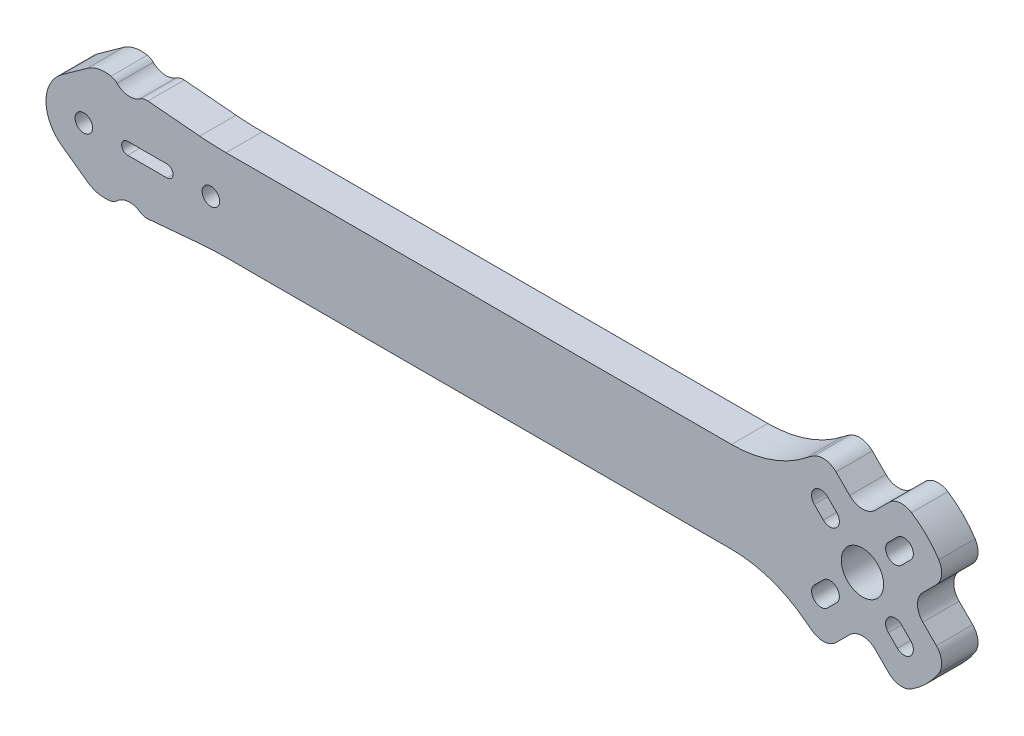
SolidWorks part; units mm, degrees
material "Thornel Mat VMA"
ref_plane "Front Plane" through (0, 0, 0) normal (0, 0, 1) x (1, 0, 0)
ref_plane "Top Plane" through (0, 0, 0) normal (0, 1, 0) x (1, 0, 0)
ref_plane "Right Plane" through (0, 0, 0) normal (1, 0, 0) x (0, 0, -1)
sketch "Sketch1" plane through (0, 0, 0) normal (0, 0, 1) x (1, 0, 0)
  line L0 (6.8589, 6.8589) -> (5.374, 5.374) construction
  line L2 (7.955, 5.7629) -> (6.47, 4.278)
  line L3 (5.7629, 7.955) -> (4.278, 6.47)
  line L4 (-6.8589, 6.8589) -> (-5.374, 5.374) construction
  line L5 (-5.7629, 7.955) -> (-4.278, 6.47)
  line L6 (-7.955, 5.7629) -> (-6.47, 4.278)
  line L7 (5.374, -5.374) -> (-5.374, 5.374) construction
  line L8 (6.8589, -6.8589) -> (5.374, -5.374) construction
  line L9 (5.7629, -7.955) -> (4.278, -6.47)
  line L11 (7.955, -5.7629) -> (6.47, -4.278)
  line L12 (-6.8589, -6.8589) -> (-5.374, -5.374) construction
  line L13 (-7.955, -5.7629) -> (-6.47, -4.278)
  line L14 (-5.7629, -7.955) -> (-4.278, -6.47)
  line L15 (-118.078, -8.4386) -> (-109.5245, -7.6903)
  line L16 (-105.1667, -7.5) -> (-21.6506, -7.5)
  line L17 (-4.367, -12.2159) -> (-2.1213, -9.9702)
  line L18 (2.1213, -9.9702) -> (4.367, -12.2159)
  line L19 (12.2159, -4.367) -> (9.9702, -2.1213)
  line L20 (9.9702, 2.1213) -> (12.2159, 4.367)
  line L21 (4.367, 12.2159) -> (2.1213, 9.9702)
  line L22 (-2.1213, 9.9702) -> (-4.367, 12.2159)
  line L23 (-21.6506, 7.5) -> (-105.1667, 7.5)
  line L24 (-109.5245, 7.6903) -> (-118.078, 8.4386)
  line L25 (-128.1078, 8.1033) -> (-132.3227, 5.0768)
  line L26 (-132.3227, -5.0768) -> (-128.1078, -8.1033)
  line L27 (-121.4272, 1) -> (-114.9272, 1)
  line L28 (-114.9272, -1) -> (-121.4272, -1)
  line L29 (0, 0) -> (-2.4749, 0) construction
  line L30 (-2.4749, 0) -> (-2.4749, 2.4749) construction
  circle A1 centre (0, 0) radius 3.5
  arc A20 (-124.1818, -8.9388) -> (-123.1893, -8.4119) centre (-124.5857, -6.98) ccw
  arc A21 (-119.3893, -8.0916) -> (-123.1893, -8.4119) centre (-121.0948, -10.5597) ccw
  arc A22 (-119.3893, -8.0916) -> (-118.078, -8.4386) centre (-118.2523, -6.4462) ccw
  arc A23 (-105.1667, -7.5) -> (-109.5245, -7.6903) centre (-105.1667, -57.5) ccw
  arc A24 (-9.2788, -11.7857) -> (-21.6506, -7.5) centre (-21.6506, -27.5) ccw
  arc A25 (-9.2788, -11.7857) -> (-8.1105, -12.6183) centre (0, 0) ccw
  arc A26 (-8.1105, -12.6183) -> (-4.367, -12.2159) centre (-6.4884, -10.0946) ccw
  arc A27 (2.1213, -9.9702) -> (-2.1213, -9.9702) centre (0, -12.0915) ccw
  arc A28 (4.367, -12.2159) -> (8.1105, -12.6183) centre (6.4884, -10.0946) ccw
  arc A29 (8.1105, -12.6183) -> (12.6183, -8.1105) centre (0, 0) ccw
  arc A30 (12.6183, -8.1105) -> (12.2159, -4.367) centre (10.0946, -6.4884) ccw
  arc A31 (9.9702, 2.1213) -> (9.9702, -2.1213) centre (12.0915, 0) ccw
  arc A32 (12.2159, 4.367) -> (12.6183, 8.1105) centre (10.0946, 6.4884) ccw
  arc A33 (12.6183, 8.1105) -> (8.1105, 12.6183) centre (0, 0) ccw
  arc A34 (8.1105, 12.6183) -> (4.367, 12.2159) centre (6.4884, 10.0946) ccw
  arc A35 (-2.1213, 9.9702) -> (2.1213, 9.9702) centre (0, 12.0915) ccw
  arc A36 (-4.367, 12.2159) -> (-8.1105, 12.6183) centre (-6.4884, 10.0946) ccw
  arc A37 (-8.1105, 12.6183) -> (-9.2788, 11.7857) centre (0, 0) ccw
  arc A38 (-21.6506, 7.5) -> (-9.2788, 11.7857) centre (-21.6506, 27.5) ccw
  arc A39 (-109.5245, 7.6903) -> (-105.1667, 7.5) centre (-105.1667, 57.5) ccw
  arc A40 (-118.078, 8.4386) -> (-119.3893, 8.0916) centre (-118.2523, 6.4462) ccw
  arc A41 (-123.1893, 8.4119) -> (-119.3893, 8.0916) centre (-121.0948, 10.5597) ccw
  arc A42 (-123.1893, 8.4119) -> (-124.1818, 8.9388) centre (-124.5857, 6.98) ccw
  arc A43 (-124.1818, 8.9388) -> (-128.1078, 8.1033) centre (-125.1915, 4.0418) ccw
  arc A44 (-132.3227, 5.0768) -> (-132.3227, -5.0768) centre (-128.6772, 0) ccw
  arc A45 (-128.1078, -8.1033) -> (-124.1818, -8.9388) centre (-125.1915, -4.0418) ccw
  arc A46 (-121.4272, 1) -> (-121.4272, -1) centre (-121.4272, 0) ccw
  arc A47 (-114.9272, -1) -> (-114.9272, 1) centre (-114.9272, 0) ccw
  arc A48 (-5.7629, 7.955) -> (-7.955, 5.7629) centre (-6.8589, 6.8589) ccw
  arc A49 (-6.47, 4.278) -> (-4.278, 6.47) centre (-5.374, 5.374) ccw
  arc A50 (7.955, 5.7629) -> (5.7629, 7.955) centre (6.8589, 6.8589) ccw
  arc A51 (4.278, 6.47) -> (6.47, 4.278) centre (5.374, 5.374) ccw
  arc A52 (5.7629, -7.955) -> (7.955, -5.7629) centre (6.8589, -6.8589) ccw
  arc A53 (6.47, -4.278) -> (4.278, -6.47) centre (5.374, -5.374) ccw
  arc A54 (-7.955, -5.7629) -> (-5.7629, -7.955) centre (-6.8589, -6.8589) ccw
  arc A55 (-4.278, -6.47) -> (-6.47, -4.278) centre (-5.374, -5.374) ccw
  point P12 (6.1165, 6.1165)
  point P21 (-6.1165, 6.1165)
  point P26 (6.1165, -6.1165)
  point P29 (0, 0)
  point P102 (-6.1165, -6.1165)
  point P107 (0, 0)
  dimension "D1" = 7
  dimension "D2" = 3.1
  dimension "D3" = 2.1
  dimension "D4" = 15.2
  dimension "D5" = 4
extrude "Boss-Extrude1" add sketch "Sketch1" along normal blind 6
hole_wizard "M2.5 Clearance Hole1" positions "Sketch2" profile "Sketch3" hole size "M2.5" standard "ANSI Metric" end condition up to next
sketch "Sketch2" plane through (0, 0, 6) normal (0, 0, 1) x (1, 0, 0)
  line L0 (-128.6772, 0) -> (-107.6772, 0) construction
  arc A0 (-132.3227, 5.0768) -> (-132.3227, -5.0768) centre (-128.6772, 0) ccw construction
  point P0 (-107.6772, 0)
  point P3 (-128.6772, 0)
  dimension "D1" = 21
sketch "Sketch3" plane through (-107.6772, 0, 6) normal (1, 0, 0) x (0, -1, 0)
  line L0 (0, 0) -> (0, 6)
  line L1 (0, 6) -> (1.45, 6)
  line L2 (1.45, 6) -> (1.45, 0)
  line L5 (1.45, 0) -> (0, 0)
  line L11 (0, -6.35) -> (0, 107.95) construction
  dimension "Thru Hole Dia." = 2.9
  dimension "Thru Hole Depth" = 6
